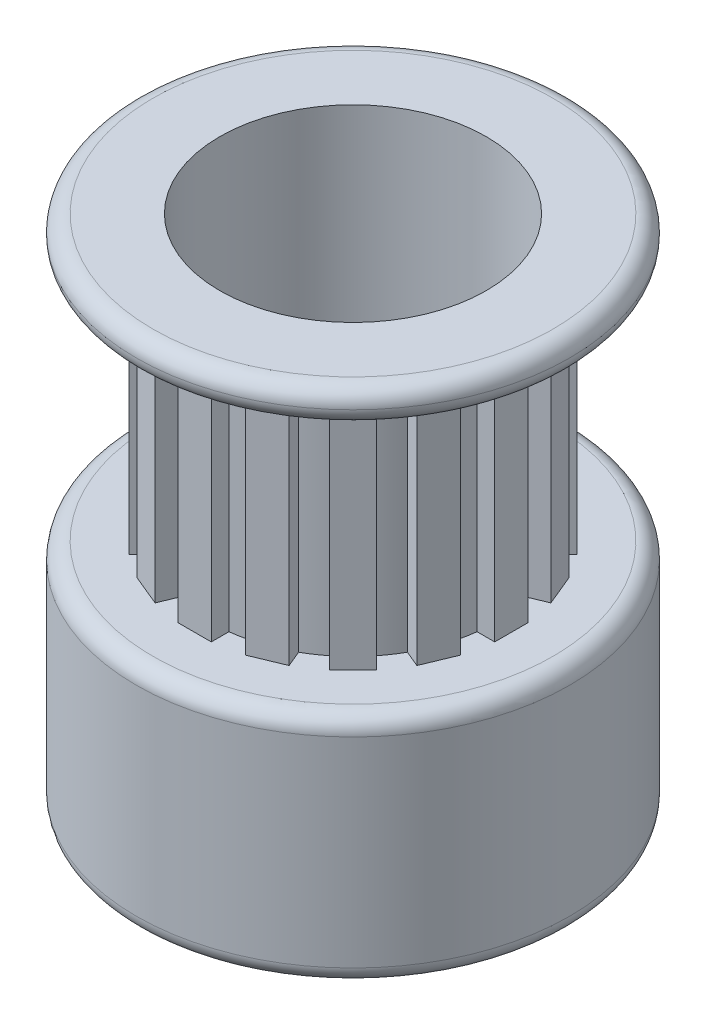
SolidWorks part; units mm, degrees
ref_plane "前基準面" through (0, 0, 0) normal (0, 0, 1) x (1, 0, 0)
ref_plane "上基準面" through (0, 0, 0) normal (0, 1, 0) x (1, 0, 0)
ref_plane "右基準面" through (0, 0, 0) normal (1, 0, 0) x (0, 0, -1)
sketch "草圖3" plane through (0, 0, 0) normal (0, 1, 0) x (1, 0, 0)
  line L0 (1355.8065, 4579.7695) -> (1153.1702, 4090.5621)
  line L1 (-500, 4750) -> (500, 4750)
  line L2 (-500, 4750) -> (-500, 4220.4858)
  line L3 (1355.8065, 4579.7695) -> (2279.6861, 4197.0861)
  line L4 (500, 4750) -> (500, 4220.4858)
  line L5 (2279.6861, 4197.0861) -> (2077.0497, 3707.8787)
  line L6 (3005.2038, 3712.3106) -> (2630.7807, 3337.8875)
  line L7 (3005.2038, 3712.3106) -> (3712.3106, 3005.2038)
  line L8 (3712.3106, 3005.2038) -> (3337.8875, 2630.7807)
  line L9 (4197.0861, 2279.6861) -> (3707.8787, 2077.0497)
  line L10 (4197.0861, 2279.6861) -> (4579.7695, 1355.8065)
  line L11 (4579.7695, 1355.8065) -> (4090.5621, 1153.1702)
  line L12 (4750, 500) -> (4220.4858, 500)
  line L13 (4750, 500) -> (4750, -500)
  line L14 (4750, -500) -> (4220.4858, -500)
  line L15 (4579.7695, -1355.8065) -> (4090.5621, -1153.1702)
  line L16 (4579.7695, -1355.8065) -> (4197.0861, -2279.6861)
  line L17 (4197.0861, -2279.6861) -> (3707.8787, -2077.0497)
  line L18 (3712.3106, -3005.2038) -> (3337.8875, -2630.7807)
  line L19 (3712.3106, -3005.2038) -> (3005.2038, -3712.3106)
  line L20 (3005.2038, -3712.3106) -> (2630.7807, -3337.8875)
  line L21 (2279.6861, -4197.0861) -> (2077.0497, -3707.8787)
  line L22 (2279.6861, -4197.0861) -> (1355.8065, -4579.7695)
  line L23 (1355.8065, -4579.7695) -> (1153.1702, -4090.5621)
  line L24 (500, -4750) -> (500, -4220.4858)
  line L25 (500, -4750) -> (-500, -4750)
  line L26 (-500, -4750) -> (-500, -4220.4858)
  line L27 (-1355.8065, -4579.7695) -> (-1153.1702, -4090.5621)
  line L28 (-1355.8065, -4579.7695) -> (-2279.6861, -4197.0861)
  line L29 (-2279.6861, -4197.0861) -> (-2077.0497, -3707.8787)
  line L30 (-3005.2038, -3712.3106) -> (-2630.7807, -3337.8875)
  line L31 (-3005.2038, -3712.3106) -> (-3712.3106, -3005.2038)
  line L32 (-3712.3106, -3005.2038) -> (-3337.8875, -2630.7807)
  line L33 (-4197.0861, -2279.6861) -> (-3707.8787, -2077.0497)
  line L34 (-4197.0861, -2279.6861) -> (-4579.7695, -1355.8065)
  line L35 (-4579.7695, -1355.8065) -> (-4090.5621, -1153.1702)
  line L36 (-4750, -500) -> (-4220.4858, -500)
  line L37 (-4750, -500) -> (-4750, 500)
  line L38 (-4750, 500) -> (-4220.4858, 500)
  line L39 (-4579.7695, 1355.8065) -> (-4090.5621, 1153.1702)
  line L40 (-4579.7695, 1355.8065) -> (-4197.0861, 2279.6861)
  line L41 (-4197.0861, 2279.6861) -> (-3707.8787, 2077.0497)
  line L42 (-3712.3106, 3005.2038) -> (-3337.8875, 2630.7807)
  line L43 (-3712.3106, 3005.2038) -> (-3005.2038, 3712.3106)
  line L44 (-3005.2038, 3712.3106) -> (-2630.7807, 3337.8875)
  line L45 (-2279.6861, 4197.0861) -> (-2077.0497, 3707.8787)
  line L46 (-2279.6861, 4197.0861) -> (-1355.8065, 4579.7695)
  line L47 (-1355.8065, 4579.7695) -> (-1153.1702, 4090.5621)
  circle A0 centre (0, 0) radius 4000
  arc A1 (-3337.8875, 2630.7807) -> (-3707.8787, 2077.0497) centre (0, 0) ccw
  arc A2 (-2077.0497, 3707.8787) -> (-2630.7807, 3337.8875) centre (0, 0) ccw
  arc A3 (-500, 4220.4858) -> (-1153.1702, 4090.5621) centre (0, 0) ccw
  arc A4 (1153.1702, 4090.5621) -> (500, 4220.4858) centre (0, 0) ccw
  arc A5 (2630.7807, 3337.8875) -> (2077.0497, 3707.8787) centre (0, 0) ccw
  arc A6 (3707.8787, 2077.0497) -> (3337.8875, 2630.7807) centre (0, 0) ccw
  arc A7 (4220.4858, 500) -> (4090.5621, 1153.1702) centre (0, 0) ccw
  arc A8 (4090.5621, -1153.1702) -> (4220.4858, -500) centre (0, 0) ccw
  arc A9 (3337.8875, -2630.7807) -> (3707.8787, -2077.0497) centre (0, 0) ccw
  arc A10 (2077.0497, -3707.8787) -> (2630.7807, -3337.8875) centre (0, 0) ccw
  arc A11 (500, -4220.4858) -> (1153.1702, -4090.5621) centre (0, 0) ccw
  arc A12 (-1153.1702, -4090.5621) -> (-500, -4220.4858) centre (0, 0) ccw
  arc A13 (-2630.7807, -3337.8875) -> (-2077.0497, -3707.8787) centre (0, 0) ccw
  arc A14 (-3707.8787, -2077.0497) -> (-3337.8875, -2630.7807) centre (0, 0) ccw
  arc A15 (-4220.4858, -500) -> (-4090.5621, -1153.1702) centre (0, 0) ccw
  arc A16 (-4090.5621, 1153.1702) -> (-4220.4858, 500) centre (0, 0) ccw
  point P71 (0, 0)
  dimension "D1" = 8000
  dimension "D3" = 8500
  dimension "D2" = 16
  dimension "D4" = 1000
extrude "填料-伸長1" add sketch "草圖3" along normal blind 7500
sketch "草圖4" plane through (0, 7500, 0) normal (0, 1, 0) x (1, 0, 0)
  circle A0 centre (0, 0) radius 4000
  circle A1 centre (0, 0) radius 6500
  dimension "D1" = 13000
extrude "填料-伸長2" add sketch "草圖4" along normal blind 1000
sketch "草圖5" plane through (0, 0, 0) normal (0, -1, 0) x (1, 0, 0)
  circle A0 centre (0, 0) radius 4000
  circle A1 centre (0, 0) radius 6500
extrude "填料-伸長3" add sketch "草圖5" along normal blind 7000
fillet "圓角1" radius 500 2 edges at (0, -7000, -6500) (0, 0, -6500)
fillet "圓角2" radius 500 2 edges at (0, 7500, 6500) (0, 8500, 6500)
sketch "草圖6" plane through (0, 0, 0) normal (1, 0, 0) x (0, 0, -1)
  circle A0 centre (0, -3000) radius 1500
  dimension "D2" = 3000
  dimension "D1" = 3000
extrude "除料-伸長1" cut sketch "草圖6" against normal blind 7000
